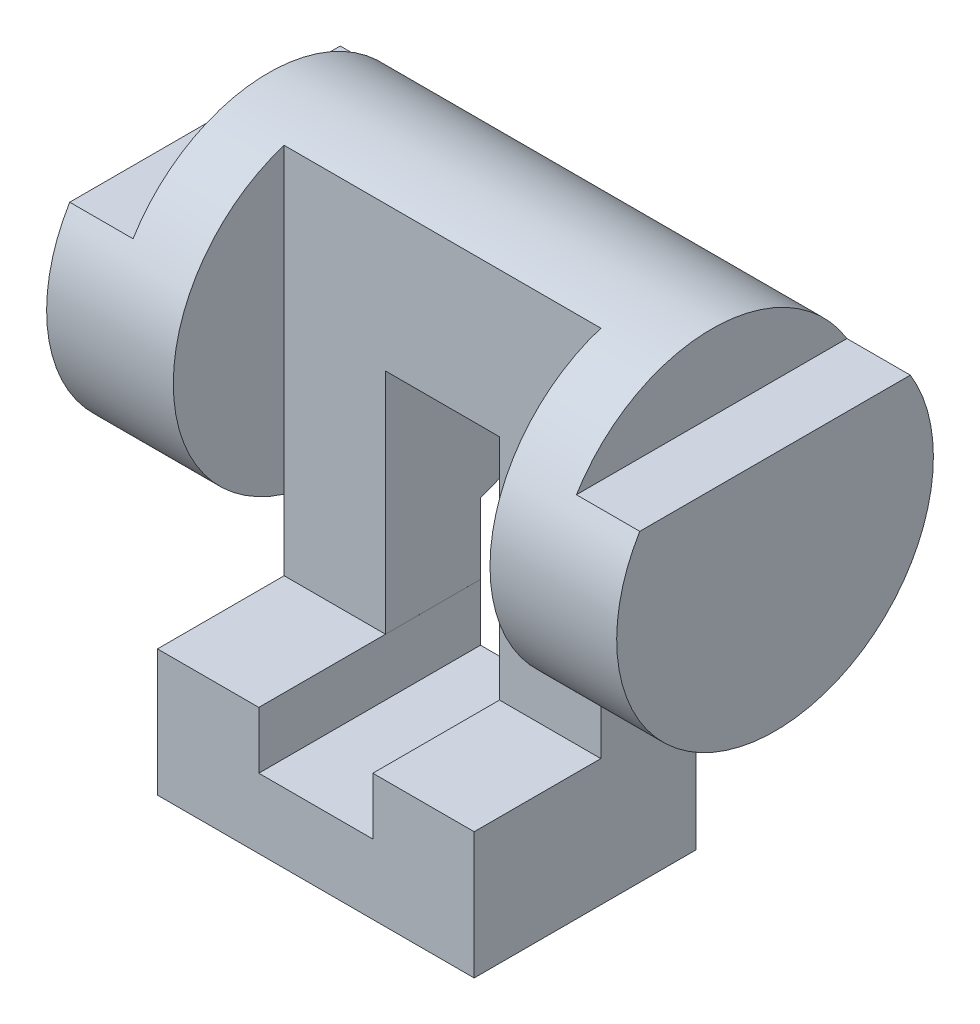
SolidWorks part; units mm, degrees
ref_plane "Спереди" through (0, 0, 0) normal (0, 0, 1) x (1, 0, 0)
ref_plane "Сверху" through (0, 0, 0) normal (0, 1, 0) x (1, 0, 0)
ref_plane "Справа" through (0, 0, 0) normal (1, 0, 0) x (0, 0, -1)
other "Configuration Table"
sketch "Эскиз1" plane through (0, 0, 0) normal (0, 0, 1) x (1, 0, 0)
  line L0 (0, 0) -> (50, 0)
  line L1 (50, 0) -> (50, 20)
  line L3 (0, 19.9997) -> (0, 0)
  line L4 (0, 19.9997) -> (16, 19.9997)
  line L5 (16, 19.9997) -> (16, 11)
  line L6 (16, 11) -> (34, 11)
  line L7 (34, 11) -> (34, 20)
  line L8 (34, 20) -> (50, 20)
  dimension "D1" = 16
  dimension "D2" = 50
  dimension "D3" = 9
  dimension "D4" = 16
  dimension "D5" = 20
  dimension "D6" = 8.9997
extrude "Бобышка-Вытянуть1" add sketch "Эскиз1" against normal blind 35
sketch "Эскиз2" plane through (0, 0, 0) normal (1, 0, 0) x (0, 0, -1)
  line L1 (35, 20) -> (20, 20)
  line L2 (35, 20) -> (35, 55)
  line L3 (35, 55) -> (20, 55)
  line L4 (20, 20) -> (20, 55)
  line L5 (35, 0) -> (0, 0) construction
  circle A1 centre (27.5, 55) radius 25
  dimension "D2" = 50
  dimension "D1" = 55
  dimension "D3" = 20
extrude "Бобышка-Вытянуть3" add sketch "Эскиз2" along normal mid plane 90 from offset 25 separate body contours L2 A1 L4 L3 | L4 A1 L2 L3 region at (0, 42.6877, -27.5) region at (0, 57.8521, -27.5)
sketch "Эскиз3" plane through (0, 0, 0) normal (1, 0, 0) x (0, 0, -1)
  line L1 (35, 20) -> (20, 20)
  line L2 (35, 20) -> (35, 55)
  line L3 (35, 55) -> (20, 55)
  line L4 (20, 20) -> (20, 55)
  circle A1 centre (27.5, 55) radius 25
  dimension "D2" = 50
extrude "Бобышка-Вытянуть4" add sketch "Эскиз3" along normal blind 50 contours A1 L4 L1 L2 | L4 A1 L2 L3 region at (0, 25.1958, -27.5) region at (0, 42.6877, -27.5)
sketch "Эскиз4" plane through (0, 0, 0) normal (1, 0, 0) x (0, 0, -1)
  line L0 (0, 20) -> (20, 20)
  line L1 (20, 20) -> (20, 80)
  line L2 (20, 80) -> (0, 80)
  line L3 (0, 80) -> (0, 20)
  dimension "D1" = 80
extrude "Вырез-Вытянуть1" cut sketch "Эскиз4" along normal blind 50
sketch "Эскиз10" plane through (0, 0, 0) normal (0, 0, 1) x (1, 0, 0)
  line L0 (16, 11) -> (34, 11)
  line L1 (34, 11) -> (34, 56)
  line L2 (34, 56) -> (16, 56)
  line L3 (16, 56) -> (16, 11)
  dimension "D1" = 18
  dimension "D2" = 45
extrude "Вырез-Вытянуть3" cut sketch "Эскиз10" against normal blind 60
sketch "Эскиз12" plane through (0, 0, 0) normal (0, 0, 1) x (1, 0, 0)
  line L0 (-20, 80) -> (-20, 68)
  line L1 (-20, 80) -> (-20, 30) construction
  line L2 (-20, 68) -> (-10, 68)
  line L3 (-10, 68) -> (-10, 80)
  line L4 (70, 80) -> (-20, 80) construction
  line L5 (-10, 80) -> (-20, 80)
  line L6 (70, 80) -> (70, 68)
  line L7 (70, 30) -> (70, 80) construction
  line L8 (70, 68) -> (60, 68)
  line L9 (60, 68) -> (60, 80)
  line L10 (60, 80) -> (70, 80)
  dimension "D1" = 12
  dimension "D2" = 10
  dimension "D3" = 10
  dimension "D4" = 12
extrude "Вырез-Вытянуть5" cut sketch "Эскиз12" against normal blind 60
sketch "Эскиз11" plane through (0, 0, 0) normal (0, 0, 1) x (1, 0, 0)
